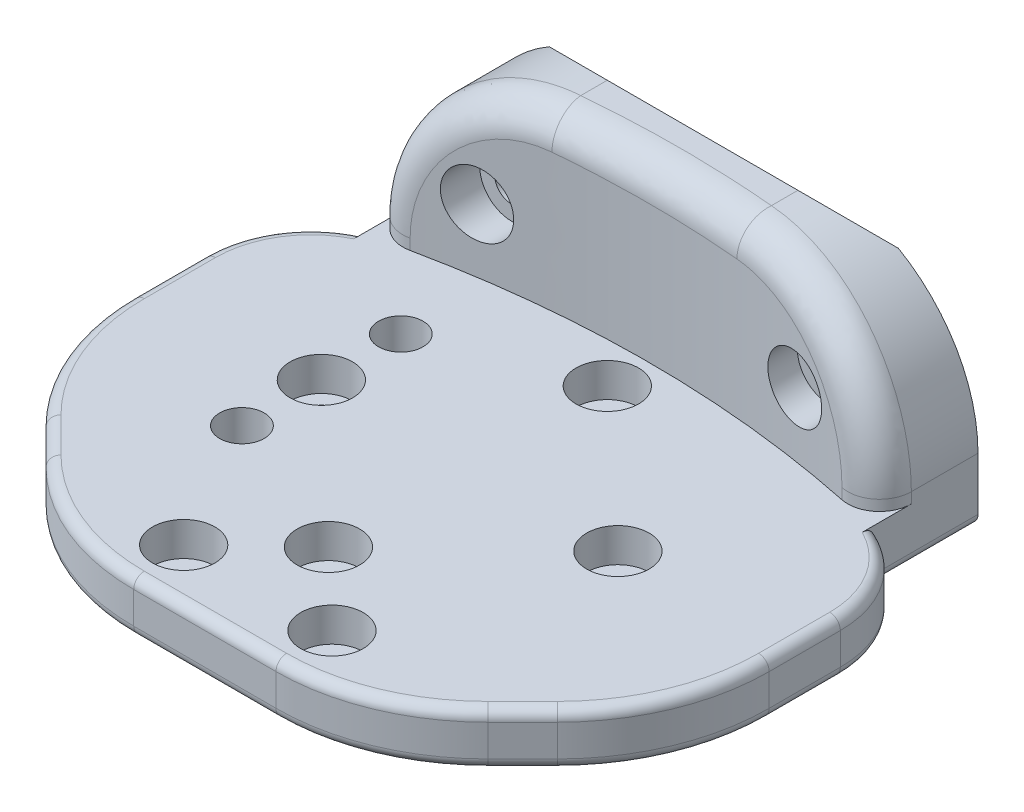
SolidWorks part; units mm, degrees
ref_plane "Alzado" through (0, 0, 0) normal (0, 0, 1) x (1, 0, 0)
ref_plane "Planta" through (0, 0, 0) normal (0, 1, 0) x (1, 0, 0)
ref_plane "Vista lateral" through (0, 0, 0) normal (1, 0, 0) x (0, 0, -1)
sketch "Croquis1" plane through (0, 0, 0) normal (0, 1, 0) x (1, 0, 0)
  line L0 (30, 40) -> (30, 0) construction
  line L1 (0, 0) -> (60, 0) construction
  line L2 (0, 0) -> (0, 40) construction
  line L3 (10, 40) -> (50, 40)
  line L4 (60, 0) -> (60, 40) construction
  line L5 (9.1421, 5.8579) -> (5.8579, 9.1421)
  line L6 (37, 25) -> (44, 25)
  line L7 (37, 25) -> (37, 5)
  line L8 (37, 5) -> (44, 5)
  line L9 (44, 25) -> (44, 5)
  line L10 (16, 25) -> (16, 5)
  line L11 (23, 5) -> (16, 5)
  line L12 (23, 25) -> (23, 5)
  line L13 (50.8579, 5.8579) -> (54.1421, 9.1421)
  line L14 (23, 25) -> (16, 25)
  line L15 (0, 23.2843) -> (0, 30)
  line L16 (60, 30) -> (60, 23.2843)
  line L17 (36.7157, 0) -> (23.2843, 0)
  line L18 (30, 40) -> (30, 44) construction
  circle A0 centre (44, 25) radius 1.6
  circle A1 centre (37, 5) radius 1.6
  circle A2 centre (23, 5) radius 1.6
  circle A3 centre (16, 25) radius 1.6
  arc A4 (50.8579, 5.8579) -> (36.7157, 0) centre (36.7157, 20) cw
  arc A5 (23.2843, 0) -> (9.1421, 5.8579) centre (23.2843, 20) cw
  arc A6 (60, 23.2843) -> (54.1421, 9.1421) centre (40, 23.2843) cw
  arc A7 (5.8579, 9.1421) -> (0, 23.2843) centre (20, 23.2843) cw
  arc A8 (60, 30) -> (50, 40) centre (50, 30) ccw
  arc A9 (10, 40) -> (0, 30) centre (10, 30) ccw
  spline S0 degree 2 poles (10, 40) (30, 48) (50, 40) knots 0 0 0 1 1 1
  point P19 (45, 0)
  point P20 (60, 15)
  point P27 (45, 0)
  point P30 (15, 0)
  point P33 (60, 15)
  point P36 (0, 15)
  dimension "D5" = 3.2
  dimension "D8" = 15
  dimension "D10" = 20
  dimension "D11" = 10
  dimension "D1" = 60
  dimension "D2" = 40
  dimension "D3" = 7
  dimension "D4" = 20
  dimension "D6" = 15
  dimension "D7" = 16
  dimension "D9" = 15
  dimension "D12" = 4
extrude "Saliente-Extruir1" add sketch "Croquis1" along normal blind 5 contours L3 A9 L15 A7 L5 A5 L17 A4 L13 A6 L16 A8 L10 A3 L14 L12 A2 L11 A1 L7 L6 A0 L9 L8 | A1 L8 L9 A0 L6 L7 | L14 A3 L10 L11 A2 L12 region at (30, 0, -22.528) region at (40.5, 0, -15) region at (19.5, 0, -15)
extrude "Saliente-Extruir2" add sketch "Croquis1<3>" along normal blind 5 contours S0 L3 region at (30, 0, -41.6)
sketch "Croquis1<3>" plane through (0, 0, 0) normal (0, 1, 0) x (1, 0, 0) same geometry as "Croquis1"
sketch "Croquis5" plane through (0, 5, 0) normal (0, 1, 0) x (1, 0, 0)
  line L0 (16, 25) -> (37, 5) construction
  line L1 (44, 25) -> (23, 5) construction
  line L2 (30, 0) -> (30, 44) construction
  line L3 (36.7157, 0) -> (23.2843, 0) construction
  circle A1 centre (30, 11.6667) radius 1.55
  circle A3 centre (30, 38) radius 1.55
  parabola Q0 (10, 40) -> (50, 40) focus (30, 19) apex (30, 44) construction
  point P16 (30, 11.6667)
  point P20 (30, 38)
  dimension "D1" = 3.1
  dimension "D3" = 6
extrude "Cortar-Extruir3" cut sketch "Croquis5" against normal blind 8
sketch "Croquis6" plane through (0, 5, 0) normal (0, 1, 0) x (1, 0, 0)
  circle A0 centre (30, 38) radius 2.95
  circle A1 centre (30, 11.6667) radius 2.95
  circle A2 centre (16, 25) radius 2.95
  circle A3 centre (44, 25) radius 2.95
  circle A4 centre (23, 5) radius 2.95
  circle A5 centre (37, 5) radius 2.95
  dimension "D1" = 5.9
extrude "Cortar-Extruir4" cut sketch "Croquis6" against normal blind 3.2
sketch "Croquis7" plane through (0, 0, 0) normal (0, -1, 0) x (1, 0, 0)
  circle A0 centre (30, -11.6667) radius 3.5
  circle A1 centre (30, -38) radius 3.5
  circle A2 centre (30, -38) radius 1.55
  circle A3 centre (30, -11.6667) radius 1.55
  dimension "D1" = 3.1
  dimension "D2" = 7
sketch "Croquis10" plane through (0, 5, 0) normal (0, 1, 0) x (1, 0, 0)
  line L3 (6, 49) -> (54, 49)
  line L4 (6, 49) -> (6, 38.95)
  line L5 (6, 38.95) -> (54, 38.95) construction
  line L6 (54, 49) -> (54, 38.95)
  line L7 (60, 30) -> (60, 23.2843) construction
  spline S0 degree 2 poles (6, 38.95) (30, 44.8394) (54, 38.95) knots 0 0 0 1 1 1
  point P0 (30, 38)
  point P11 (30, 41.8947)
  dimension "D1" = 48
  dimension "D2" = 10.05
  dimension "D3" = 0.95
  dimension "D4" = 6
extrude "Saliente-Extruir4" add sketch "Croquis10" along normal blind 16 and the other way up to surface (5 mm away) other way up to face at (30, 0, -36.45)
fillet "Redondeo2" radius 15 2 edges at (54, 21, -43.975) (6, 21, -43.975)
sketch "Croquis11" plane through (0, 0, -49) normal (0, 0, -1) x (-1, 0, 0)
  line L0 (-30, 21) -> (-30, 0) construction
  line L1 (-39, 21) -> (-21, 21) construction
  line L2 (-6, 0) -> (-54, 0) construction
  line L3 (-45, 0) -> (-30, 0) construction
  line L4 (-45, 11) -> (-15, 11) construction
  line L5 (-45, 11) -> (-45, 0) construction
  line L6 (-30, 0) -> (-15, 0) construction
  line L7 (-15, 11) -> (-15, 0) construction
  circle A0 centre (-45, 11) radius 1.6
  circle A1 centre (-15, 11) radius 1.6
  point P10 (-30, 11)
  dimension "D3" = 3.2
  dimension "D1" = 11
  dimension "D2" = 30
extrude "Cortar-Extruir5" cut sketch "Croquis11" against normal blind 8
ref_plane "Plano1" through (0, 0, -38.95) normal (0, 0, -1) x (-1, 0, 0)
sketch "Croquis12" plane through (0, 0, -38.95) normal (0, 0, -1) x (-1, 0, 0)
  circle A1 centre (-15, 11) radius 3
  circle A2 centre (-45, 11) radius 3
  dimension "D1" = 6
extrude "Cortar-Extruir6" cut sketch "Croquis12" along normal blind 5
sketch "Croquis13" plane through (0, 5, 0) normal (0, 1, 0) x (1, 0, 0)
  line L0 (16, 27.95) -> (16, 22.05) construction
  line L1 (16, 27.95) -> (16, 38.95) construction
  line L2 (11.55, 38.95) -> (-11.55, 38.95) construction
  line L3 (16, 22.05) -> (16, 1.3737) construction
  circle A0 centre (16, 25) radius 2.95 construction
  circle A1 centre (16, 25) radius 2.95 construction
  arc A2 (9.1421, 5.8579) -> (23.2843, 0) centre (23.2843, 20) ccw construction
  circle A3 centre (16, 25) radius 7.5 construction
  circle A4 centre (16, 32.5) radius 2.1
  circle A5 centre (16, 17.5) radius 2.1
  point P18 (16, 17.5)
  point P19 (16, 32.5)
  dimension "D1" = 15
  dimension "D2" = 4.2
extrude "Cortar-Extruir7" cut sketch "Croquis13" against normal blind 10
fillet "Redondeo3" radius 1 11 edges at (58.3666, 5, -35.4772) (60, 5, -26.6421) (58.4776, 5, -15.6306) (52.5, 5, -7.5) (44.3694, 5, -1.5224) (1.6334, 5, -35.4772) (0, 5, -26.6421) (1.5224, 5, -15.6306) (7.5, 5, -7.5) (15.6306, 5, -1.5224) (30, 5, 0)
fillet "Redondeo4" radius 3 5 edges at (11.6221, 17.7071, -40.168) (50.8489, 15.198, -39.6725) (6, 5.5, -38.95) (54, 5.5, -38.95)
fillet "Redondeo5" radius 1 11 edges at (58.3666, 0, -35.4772) (60, 0, -26.6421) (58.4776, 0, -15.6306) (52.5, 0, -7.5) (44.3694, 0, -1.5224) (1.6334, 0, -35.4772) (0, 0, -26.6421) (1.5224, 0, -15.6306) (7.5, 0, -7.5) (15.6306, 0, -1.5224) (30, 0, 0)
fillet "Redondeo6" radius 1 2 edges at (6, 0, -43.5311) (54, 0, -43.5311)
sketch "Sketch1" plane through (6, 0, 0) normal (-1, 0, 0) x (0, 0, 1)
  line L0 (-49, 19) -> (-47, 21)
  line L1 (-49, 21) -> (-49, 6) construction
  line L2 (-49, 21) -> (-44.4929, 21) construction
  line L3 (-47, 21) -> (-49, 21)
  line L4 (-49, 21) -> (-49, 19)
  dimension "D1" = 2
extrude "Cut-Extrude1" cut sketch "Sketch1" against normal through all
